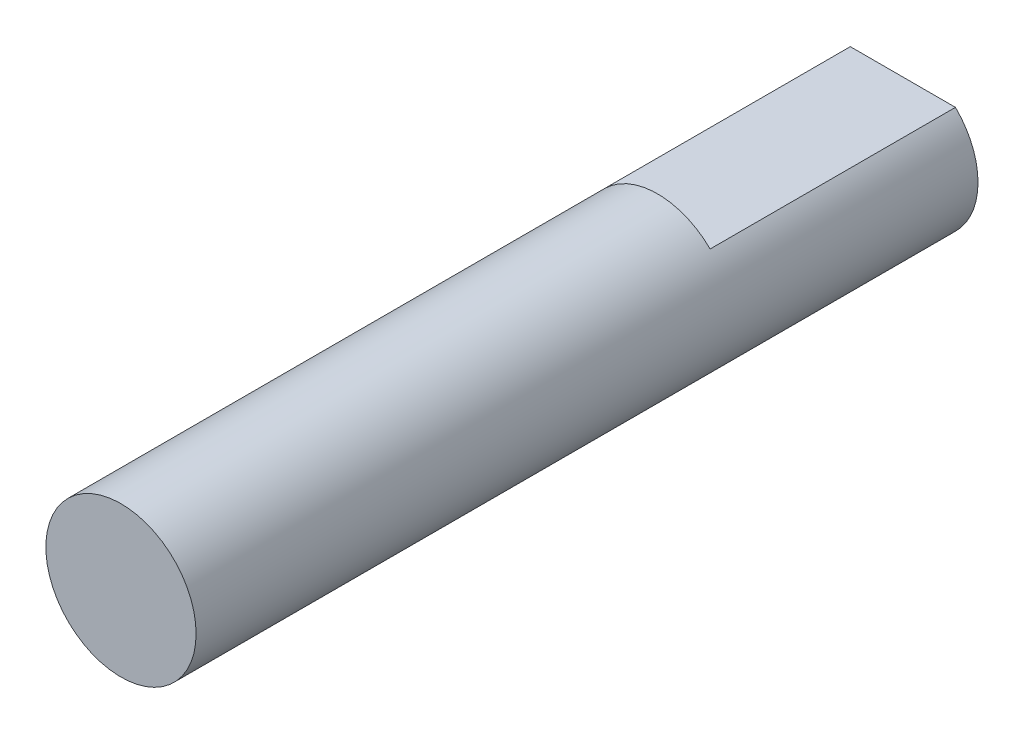
SolidWorks part; units mm, degrees
ref_plane "Alzado" through (0, 0, 0) normal (0, 0, 1) x (1, 0, 0)
ref_plane "Planta" through (0, 0, 0) normal (0, 1, 0) x (1, 0, 0)
ref_plane "Vista lateral" through (0, 0, 0) normal (1, 0, 0) x (0, 0, -1)
sketch "Croquis1" plane through (0, 0, 0) normal (0, 0, 1) x (1, 0, 0)
  circle A0 centre (0, 0) radius 2.45
  dimension "D1" = 4.9
extrude "Saliente-Extruir1" add sketch "Croquis1" along normal blind 18.75 and the other way blind 18.75
ref_plane "Plano1" through (0, 0, 10.74) normal (0, 0, 1) x (1, 0, 0)
sketch "Croquis3" plane through (0, 0, 18.75) normal (0, 0, 1) x (1, 0, 0)
  line L0 (0, 0) -> (0, 1.7086) construction
  line L1 (0, 0) -> (1.8187, 0) construction
  line L2 (-1.7146, 1.75) -> (1.7146, 1.75)
  line L3 (-1.7146, -1.75) -> (1.7146, -1.75)
  arc A0 (1.7146, 1.75) -> (-1.7146, 1.75) centre (0, 0) ccw
  arc A1 (-1.7146, -1.75) -> (1.7146, -1.75) centre (0, 0) ccw
  circle A2 centre (0, 0) radius 1
  point P9 (0, 1.75)
  dimension "D2" = 2
  dimension "D1" = 1.75
extrude "Cortar-Extruir1" cut sketch "Croquis3" against normal blind 8
mirror "Simetría1" about plane through (0, 0, 0) normal (0, 0, 1) of "Cortar-Extruir1"
sketch "Szkic2" plane through (0, 0, 18.75) normal (0, 0, 1) x (1, 0, 0)
  line L1 (2.5, -2.5) -> (-2.5, -2.5)
  line L2 (2.5, -2.5) -> (2.5, 2.5)
  line L3 (2.5, 2.5) -> (-2.5, 2.5)
  line L4 (-2.5, -2.5) -> (-2.5, 2.5)
  line L5 (2.5, -2.5) -> (-2.5, 2.5) construction
  line L6 (2.5, 2.5) -> (-2.5, -2.5) construction
  point P0 (0, 0)
  dimension "D1" = 5
  dimension "D2" = 5
extrude "Wytnij-wyciągnięcie1" cut sketch "Szkic2" against normal blind 12
